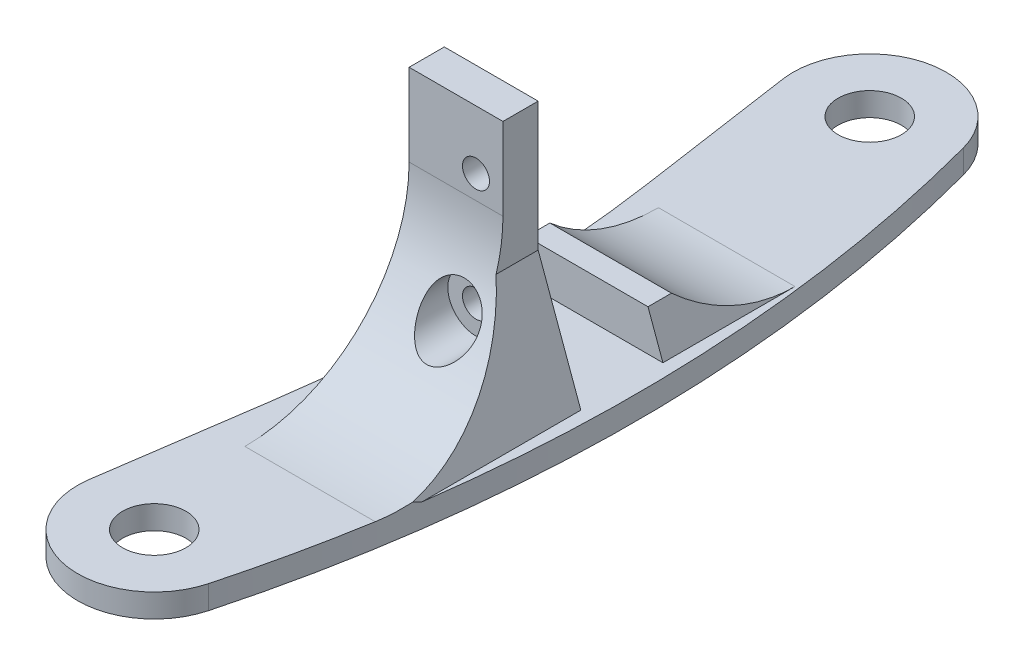
SolidWorks part; units mm, degrees
ref_plane "Front Plane" through (0, 0, 0) normal (0, 0, 1) x (1, 0, 0)
ref_plane "Top Plane" through (0, 0, 0) normal (0, 1, 0) x (1, 0, 0)
ref_plane "Right Plane" through (0, 0, 0) normal (1, 0, 0) x (0, 0, -1)
sketch "Sketch1" plane through (0, 0, 0) normal (0, 0, 1) x (1, 0, 0)
  line L0 (1, 3) -> (11, 3) construction
  line L1 (11, 23) -> (3, 23)
  line L2 (11, 23) -> (11, 2)
  line L3 (11, 2) -> (3, 2)
  line L4 (3, 23) -> (3, 2)
  line L5 (11, 5.5) -> (3, 5.5)
  circle A0 centre (8.7, 18) radius 1.15
  circle A1 centre (8.7, 8.4) radius 1.15
  dimension "D1" = 1
  dimension "D2" = 3.5
  dimension "D3" = 8
extrude "Boss-Extrude1" add sketch "Sketch1" along normal blind 3 contours L5 L2 L1 L4 A1 A0 | L2 L5 L4 L3 region at (6.8927, 14.3163, 0) region at (7, 3.75, 0)
sketch "Sketch2" plane through (0, 0, 0) normal (0, 1, 0) x (1, 0, 0)
  line L0 (0.7878, -12.4454) -> (-1.197, -26.0524)
  line L1 (15.8135, 3.5055) -> (-4.8175, 3.5055) construction
  line L2 (0.7878, 19.4564) -> (-1.197, 33.0634)
  arc A0 (11.5755, -28.6858) -> (11.5755, 35.6967) centre (-108.5639, 3.5055) ccw
  arc A1 (0.7878, -12.4454) -> (0.7878, 19.4564) centre (-108.5639, 3.5055) ccw
  arc A2 (-1.197, -26.0524) -> (11.5755, -28.6858) centre (5.2663, -26.9952) ccw
  arc A4 (-28.4306, -72.5923) -> (-2.6169, -27.9184) centre (-108.5639, 3.5055) ccw construction
  arc A5 (-1.197, 33.0634) -> (11.5755, 35.6967) centre (5.2663, 34.0062) cw
  circle A6 centre (5.2663, 34.0062) radius 2.7
  circle A7 centre (5.2663, -26.9952) radius 2.7
extrude "Boss-Extrude2" add sketch "Sketch2" along normal up to surface (2 mm away) up to face at (7, 2, 1.5)
extrude "Boss-Extrude3" add sketch "Sketch1<3>" against normal blind 2 from offset 7 contours L2 L5 L4 L3 region at (7, 3.75, 0) offset against normal yes
sketch "Sketch1<3>" plane through (0, 0, 0) normal (0, 0, 1) x (1, 0, 0) same geometry as "Sketch1"
fillet "Fillet1" radius 14 2 edges at (7, 2, -9) (7, 2, 3)
chamfer "Chamfer1" distance 10 angle 20 2 edges at (11, 2, 8.5) (11, 2, -12.6301) first distance on face at (11, 12.6201, 4.0201) first distance on face at (11, 3.5385, -10.2351)
sketch "Sketch3" plane through (0, 0, 0) normal (0, 0, -1) x (-1, 0, 0)
  circle A0 centre (-8.7, 8.4) radius 2.4
extrude "Cut-Extrude1" cut sketch "Sketch3" along normal up to surface (-3 mm away) from offset 10 up to face at (9.85, 18, 3) offset against normal yes
